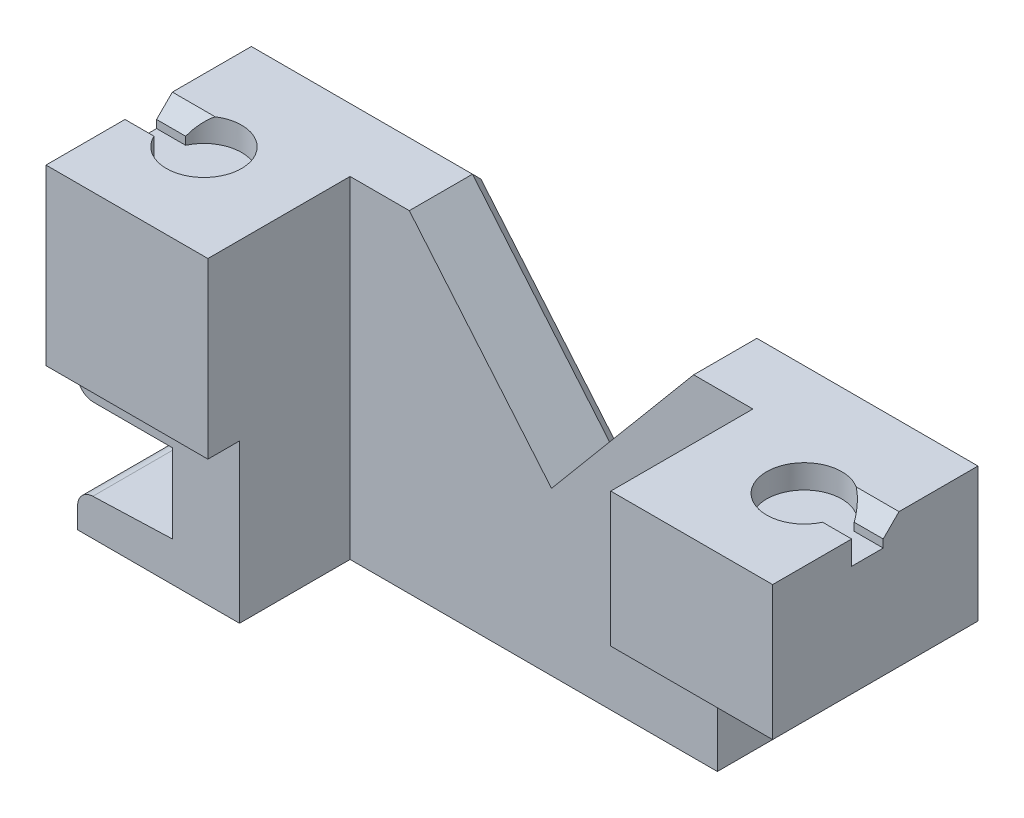
SolidWorks part; units mm, degrees
ref_plane "Front Plane" through (0, 0, 0) normal (0, 0, 1) x (1, 0, 0)
ref_plane "Top Plane" through (0, 0, 0) normal (0, 1, 0) x (1, 0, 0)
ref_plane "Right Plane" through (0, 0, 0) normal (1, 0, 0) x (0, 0, -1)
sketch "Sketch2" plane through (0, 0, 0) normal (0, 0, 1) x (1, 0, 0)
  line L1 (-12, 3) -> (-12, 12)
  line L2 (-12, 12) -> (-23, 12)
  line L3 (-23, 12) -> (-23, 0)
  line L4 (-23, 0) -> (23, 0)
  line L5 (23, 0) -> (23, 12)
  line L6 (12, 3) -> (-12, 3)
  line L8 (0, 0) -> (0, 3) construction
  line L9 (12, 3) -> (12, 12)
  line L10 (12, 12) -> (23, 12)
  dimension "D3" = 3
  dimension "D1" = 46
  dimension "D2" = 9
  dimension "D5" = 12
extrude "Boss-Extrude1" add sketch "Sketch2" along normal mid plane 19 contours L4 L8 L6 L1 L2 L3 | L8 L4 L5 L6 region at (-15.0357, 5.0357, 0) region at (15.0357, 5.0357, 0)
sketch "Sketch3" plane through (0, 0, 9.5) normal (0, 0, 1) x (1, 0, 0)
  line L0 (-2.6212, 0) -> (-0.8192, -2.5736)
  line L1 (-23, 0) -> (23, 0) construction
  line L2 (0.8192, -2.5736) -> (2.6212, 0)
  line L3 (2.6212, 0) -> (-2.6212, 0)
  line L4 (0, -3.7434) -> (0, 0) construction
  arc A0 (-0.8192, -2.5736) -> (0.8192, -2.5736) centre (0, -2) ccw
  dimension "D1" = 1
  dimension "D3" = 3
  dimension "D2" = 70
extrude "Boss-Extrude2" [suppressed] add sketch "Sketch3" against normal up to surface (18 mm away)
sketch "Sketch4" plane through (23, 0, 0) normal (1, 0, 0) x (0, 0, -1)
  line L4 (9.5, 0) -> (9.5, 12)
  line L5 (9.5, 12) -> (-9.5, 12)
  line L6 (-9.5, 12) -> (-9.5, 0)
  line L7 (-9.5, 0) -> (9.5, 0)
  line L8 (9.5, 0) -> (9.5, 12)
  line L10 (-9.5, 12) -> (-9.5, 0)
  line L11 (-9.5, 0) -> (9.5, 0)
  line L12 (9.5, 12) -> (-9.5, 12)
  dimension "D1" = 0
sketch "Sketch5" plane through (0, 12, 0) normal (0, 1, 0) x (1, 0, 0)
  line L0 (-19, 1.5) -> (19, 1.5) construction
  line L1 (0, 1.5) -> (0, 0) construction
  circle A0 centre (-19, 1.5) radius 2.3813
  circle A1 centre (19, 1.5) radius 2.3813
  dimension "D1" = 4.7625
  dimension "D2" = 38
  dimension "D3" = 1.5
extrude "Cut-Extrude1" cut sketch "Sketch5" against normal blind 1.5
sketch "Sketch9" plane through (0, 0, 0) normal (0, -1, 0) x (1, 0, 0)
  line L0 (-23, -9.5) -> (23, -9.5) construction
  line L1 (-10.5, -4.5) -> (10.5, -4.5)
  line L2 (-10.5, -4.5) -> (-10.5, -9.5)
  line L3 (-10.5, -9.5) -> (10.5, -9.5)
  line L4 (10.5, -4.5) -> (10.5, -9.5)
  line L5 (0, -9.5) -> (0, -4.5) construction
  line L6 (-10.5, -7) -> (10.5, -7) construction
  line L7 (0, 0) -> (0, -4.5) construction
  point P128 (0, -7)
  dimension "D1" = 5
  dimension "D2" = 21
extrude "Boss-Extrude6" add sketch "Sketch9" along normal blind 9
sketch "Sketch10" plane through (0, 0, 0) normal (0, -1, 0) x (1, 0, 0)
  line L0 (-23, 9.5) -> (23, 9.5) construction
  line L1 (-10.5, -4.5) -> (10.5, -4.5)
  line L2 (-10.5, -4.5) -> (-10.5, 9.5)
  line L3 (-10.5, 9.5) -> (10.5, 9.5)
  line L4 (10.5, -4.5) -> (10.5, 9.5)
  line L5 (0, 9.5) -> (0, -4.5) construction
  line L6 (-10.5, 2.5) -> (10.5, 2.5) construction
  point P136 (0, 2.5)
extrude "Cut-Extrude4" cut sketch "Sketch10" against normal through all
sketch "Sketch11" plane through (0, 0, 9.5) normal (0, 0, 1) x (1, 0, 0)
  line L6 (10.5, 3) -> (10.5, 0)
  line L7 (10.5, 0) -> (23, 0)
  line L8 (23, 0) -> (23, 12)
  line L9 (23, 12) -> (12, 12)
  line L10 (12, 12) -> (12, 3)
  line L11 (12, 3) -> (10.5, 3)
  line L12 (10.5, 3) -> (10.5, 0)
  line L13 (10.5, 0) -> (23, 0)
  line L14 (23, 0) -> (23, 12)
  line L15 (23, 12) -> (12, 12)
  line L16 (12, 12) -> (12, 3)
  line L17 (12, 3) -> (10.5, 3)
  line L18 (-10.5, 0) -> (-10.5, 3)
  line L19 (-10.5, 3) -> (-12, 3)
  line L20 (-12, 3) -> (-12, 12)
  line L21 (-12, 12) -> (-23, 12)
  line L22 (-23, 12) -> (-23, 0)
  line L23 (-23, 0) -> (-10.5, 0)
  line L24 (-10.5, 0) -> (-10.5, 3)
  line L25 (-10.5, 3) -> (-12, 3)
  line L26 (-12, 3) -> (-12, 12)
  line L27 (-12, 12) -> (-23, 12)
  line L28 (-23, 12) -> (-23, 0)
  line L29 (-23, 0) -> (-10.5, 0)
  dimension "D1" = 0
  dimension "D2" = 0
extrude "Cut-Extrude5" cut sketch "Sketch11" against normal blind 5
sketch "Sketch12" plane through (0, 0, -9.5) normal (0, 0, -1) x (-1, 0, 0)
  line L1 (-12, 3) -> (12, 3)
  line L2 (-12, 3) -> (-12, 12)
  line L3 (-12, 12) -> (12, 12)
  line L4 (12, 3) -> (12, 12)
  line L5 (0, 12) -> (0, 3) construction
  line L6 (-12, 7.5) -> (12, 7.5) construction
  point P184 (0, 7.5)
extrude "Boss-Extrude7" add sketch "Sketch12" against normal blind 5
sketch "Sketch13" plane through (0, 0, -4.5) normal (0, 0, 1) x (1, 0, 0)
  line L0 (-9, 12) -> (0, 1.2742)
  line L1 (-12, 12) -> (12, 12) construction
  line L2 (0, 1.2742) -> (9, 12)
  line L3 (9, 12) -> (-9, 12)
  line L4 (0, 1.2742) -> (0, 12) construction
  dimension "D1" = 50
  dimension "D2" = 18
extrude "Cut-Extrude6" cut sketch "Sketch13" against normal blind 6
sketch "Sketch15" plane through (0, 0, -4.5) normal (0, 0, 1) x (1, 0, 0)
  line L0 (-23, 12) -> (-23, 0) construction
  line L1 (-23, 3.5) -> (23, 3.5)
  line L2 (-23, 3.5) -> (-23, 0)
  line L3 (-23, 0) -> (23, 0)
  line L4 (23, 3.5) -> (23, 0)
  line L5 (0, 0) -> (0, 3.5) construction
  line L6 (-23, 1.75) -> (23, 1.75) construction
  line L7 (21.3812, 10.5) -> (16.6187, 10.5) construction
  point P224 (0, 1.75)
  dimension "D1" = 7
extrude "Cut-Extrude7" cut sketch "Sketch15" along normal blind 16.5
sketch "Sketch16" plane through (0, 0, -4.5) normal (0, 0, 1) x (1, 0, 0)
  line L1 (-10.5, 0) -> (-23, 0)
  line L2 (-10.5, 0) -> (-10.5, 3.5)
  line L3 (-10.5, 3.5) -> (-23, 3.5)
  line L4 (-23, 0) -> (-23, 3.5)
  line L5 (-16.75, 3.5) -> (-16.75, 0) construction
  line L6 (-10.5, 1.75) -> (-23, 1.75) construction
  line L7 (10.5, 0) -> (23, 0)
  line L8 (10.5, 0) -> (10.5, 3.5)
  line L9 (10.5, 3.5) -> (23, 3.5)
  line L10 (23, 0) -> (23, 3.5)
  line L11 (16.75, 3.5) -> (16.75, 0) construction
  line L12 (10.5, 1.75) -> (23, 1.75) construction
  point P116 (-16.75, 1.75)
  point P143 (16.75, 1.75)
extrude "Cut-Extrude8" cut sketch "Sketch16" against normal blind 16.5
sketch "Sketch17" plane through (0, 0, -9.5) normal (0, 0, -1) x (-1, 0, 0)
  line L0 (0, 0) -> (0, -9) construction
  line L1 (10.5, -9) -> (-10.5, -9) construction
  line L19 (10.5, 3.5) -> (23, 3.5)
  line L20 (10.5, -9) -> (10.5, 3.5)
  line L21 (23, -9) -> (10.5, -9)
  line L22 (23, -6.7095) -> (23, -9)
  line L23 (17, -6.5) -> (23, -6.7095)
  line L24 (17, -1.5) -> (17, -6.5)
  line L25 (23, -1.5) -> (17, -1.5)
  line L26 (23, 3.5) -> (23, -1.5)
  line L27 (10.5, -9) -> (10.5, 3.5) construction
  line L28 (23, 12) -> (23, 3.5) construction
  line L29 (10.5, 3.5) -> (23, 3.5) construction
  dimension "D3" = 5
  dimension "D1" = 2
  dimension "D2" = 6
  dimension "D4" = 5
extrude "Boss-Extrude8" add sketch "Sketch17" against normal up to surface (5 mm away) up to face at (0, 4.1158, -4.5)
sketch "Sketch18" plane through (0, 0, -4.5) normal (0, 0, 1) x (1, 0, 0)
  line L0 (-12, 12) -> (-23, 12) construction
  line L1 (-12.75, 12) -> (12.75, 12)
  line L2 (-12.75, 12) -> (-12.75, 3.5)
  line L3 (-12.75, 3.5) -> (12.75, 3.5)
  line L4 (12.75, 12) -> (12.75, 3.5)
  line L5 (0, 3.5) -> (0, 12) construction
  line L6 (-12.75, 7.75) -> (12.75, 7.75) construction
  line L8 (12, 3.5) -> (23, 3.5) construction
  point P164 (0, 7.75)
  dimension "D1" = 12.75
extrude "Cut-Extrude9" cut sketch "Sketch18" along normal up to surface (9 mm away) up to face at (-17.5, 7.75, 4.5)
sketch "Sketch19" plane through (0, 0, -4.5) normal (0, 0, 1) x (1, 0, 0)
  line L2 (-23, 3.5) -> (-12.75, 3.5)
  line L3 (-12.75, 3.5) -> (-12.75, -9)
  line L4 (10.5, -9) -> (-23, -9) construction
  line L11 (-9, 12) -> (-12.75, 12)
  line L12 (-12.75, 12) -> (-12.75, 3.5)
  line L13 (-12.75, 3.5) -> (-23, 3.5)
  line L14 (-23, 3.5) -> (-23, -1.5)
  line L15 (-23, -9) -> (10.5, -9)
  line L17 (10.5, 3.5) -> (12.75, 3.5)
  line L18 (12.75, 3.5) -> (12.75, 12)
  line L19 (12.75, 12) -> (9, 12)
  line L20 (9, 12) -> (0, 1.2742)
  line L21 (0, 1.2742) -> (-9, 12)
  line L38 (-23, 3.5) -> (-23, -1.5)
  line L40 (-23, -1.5) -> (-17, -1.5)
  line L42 (-23, -1.5) -> (-17, -1.5)
  line L44 (-17, -1.5) -> (-17, -6.5)
  line L48 (-17, -1.5) -> (-17, -6.5)
  line L49 (-17, -6.5) -> (-23, -6.7095)
  line L50 (-17, -6.5) -> (-23, -6.7095)
  line L51 (-23, -6.7095) -> (-23, -9)
  line L52 (-23, -6.7095) -> (-23, -9)
  line L53 (10.5, -9) -> (10.5, 3.5)
  line M16 (-12.75, 3.5) -> (-23, 3.5)
  line M19 (-23, -9) -> (10.5, -9)
  line M38 (-23, 3.5) -> (-23, -1.5)
  line M39 (-23, -1.5) -> (-17, -1.5)
  line M40 (-17, -1.5) -> (-17, -6.5)
  line M41 (-17, -6.5) -> (-23, -6.7095)
  line M42 (-23, -6.7095) -> (-23, -9)
  dimension "D1" = 0
extrude "Boss-Extrude9" add sketch "Sketch19" along normal up to surface (9 mm away) contours L3 M16 M38 M39 M40 M41 M42 M19 region at (-17.875, 3.3383, -4.5) up to face at (-17.875, 7.75, 4.5)
fillet "Fillet1" radius 1 2 edges at (-23, -1.5, -2.5) (-23, -6.7095, -2.5)
sketch "Sketch20" plane through (0, 0, 4.5) normal (0, 0, 1) x (1, 0, 0)
  line L0 (-23, 12) -> (-23, -0.5) construction
  line L1 (-12.75, -9) -> (-23, -9)
  line L2 (-12.75, -9) -> (-12.75, 1)
  line L3 (-12.75, 1) -> (-23, 1)
  line L4 (-23, -9) -> (-23, 1)
  line L5 (-17.875, 1) -> (-17.875, -9) construction
  line L6 (-12.75, -4) -> (-23, -4) construction
  point P208 (-17.875, -4)
  dimension "D1" = 10
extrude "Cut-Extrude10" cut sketch "Sketch20" against normal blind 2
sketch "Sketch23" plane through (0, 12, 0) normal (0, 1, 0) x (1, 0, 0)
  line L0 (-23, -4.5) -> (-23, 9.5) construction
  line L1 (-21.1611, 2.5) -> (-23, 2.5)
  line L2 (-21.1611, 2.5) -> (-21.1611, 0.5)
  line L3 (-21.1611, 0.5) -> (-23, 0.5)
  line L4 (-23, 2.5) -> (-23, 0.5)
  line L5 (-22.0805, 0.5) -> (-22.0805, 2.5) construction
  line L6 (-21.1611, 1.5) -> (-23, 1.5) construction
  line L7 (23, -4.5) -> (23, 9.5) construction
  line L8 (21.1611, 2.5) -> (23, 2.5)
  line L9 (21.1611, 2.5) -> (21.1611, 0.5)
  line L10 (21.1611, 0.5) -> (23, 0.5)
  line L11 (23, 2.5) -> (23, 0.5)
  line L12 (22.0805, 0.5) -> (22.0805, 2.5) construction
  line L13 (21.1611, 1.5) -> (23, 1.5) construction
  circle A0 centre (-19, 1.5) radius 2.3813 construction
  circle A1 centre (19, 1.5) radius 2.3813 construction
  circle A2 centre (19, 1.5) radius 2.3813 construction
  circle A3 centre (-19, 1.5) radius 2.3813 construction
  point P16 (20.1858, -0.565)
  point P19 (-20.857, 0.0094)
  point P108 (-22.0805, 1.5)
  point P121 (22.0805, 1.5)
  dimension "D1" = 2
extrude "Cut-Extrude11" cut sketch "Sketch23" against normal up to surface (1.5 mm away) up to face at (-21.3813, 10.5, -1.5)
chamfer "Chamfer1" distance 1 angle 45 2 edges at (22.0805, 12, -2.5) (-22.0805, 12, -2.5)
chamfer "Chamfer2" distance 1 angle 45 15 edges at (-17, -4, -9.5) (-19.5174, -6.5879, -9.5) (-22.7193, -6.9806, -9.5) (-23, -8.3376, -9.5) (-6.25, -9, -9.5) (10.5, -2.75, -9.5) (16.75, 3.5, -9.5) (23, 7.75, -9.5) (16, 12, -9.5) (4.5, 6.6371, -9.5) (-4.5, 6.6371, -9.5) (-16, 12, -9.5) (-23, 5.75, -9.5) (-22.7071, -1.2071, -9.5) (-19.5, -1.5, -9.5)
